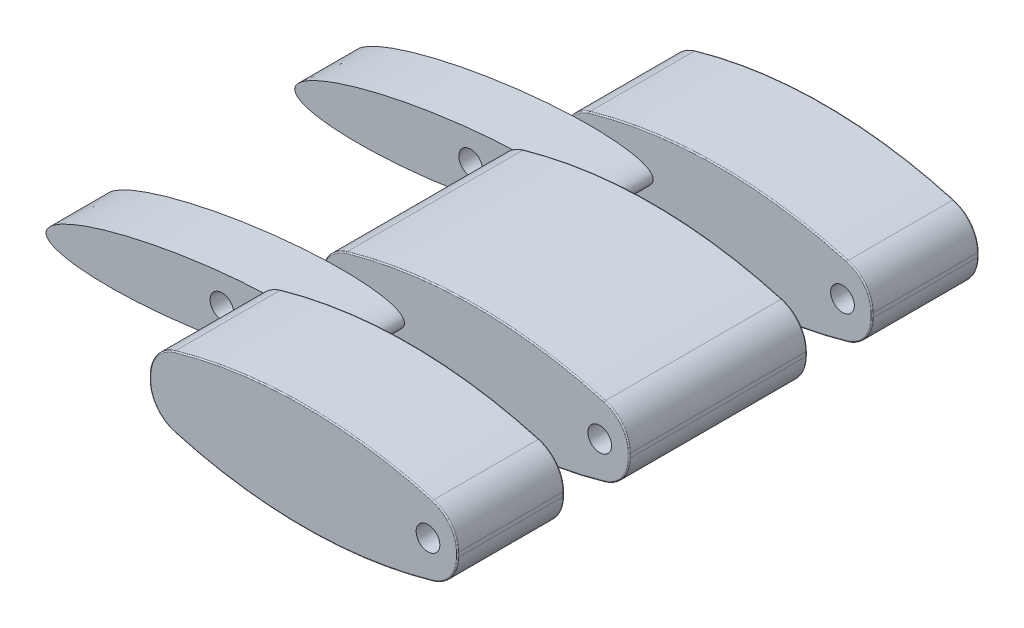
SolidWorks part; units mm, degrees
note: The reader was unsure of these and kept them because the rebuilt part matched: shared geometry of "Sketch6<2>".
ref_plane "Front Plane" through (0, 0, 0) normal (0, 0, 1) x (1, 0, 0)
ref_plane "Top Plane" through (0, 0, 0) normal (0, 1, 0) x (1, 0, 0)
ref_plane "Right Plane" through (0, 0, 0) normal (1, 0, 0) x (0, 0, -1)
sketch "Sketch1" plane through (0, 0, 0) normal (0, 0, 1) x (1, 0, 0)
  line L0 (0, -55) -> (0, 55) construction
  line L2 (-6.5, 0.0896) -> (-6.5, -0.0896)
  line L4 (6.5, 0.0896) -> (6.5, -0.0896)
  arc A0 (-5.45, 1.4833) -> (5.45, 1.4833) centre (0, -17.5045) cw
  arc A1 (-5.45, -1.4833) -> (5.45, -1.4833) centre (0, 17.5045) ccw
  arc A2 (5.45, 1.4833) -> (6.5, 0.0896) centre (5.05, 0.0896) cw
  arc A3 (5.45, -1.4833) -> (6.5, -0.0896) centre (5.05, -0.0896) ccw
  arc A4 (-5.45, -1.4833) -> (-6.5, -0.0896) centre (-5.05, -0.0896) cw
  arc A5 (-5.45, 1.4833) -> (-6.5, 0.0896) centre (-5.05, 0.0896) ccw
  dimension "D1" = 1.45
  dimension "D2" = 6.5
extrude "Boss-Extrude1" add sketch "Sketch1" along normal blind 22
sketch "Sketch2" plane through (0, 0, 0) normal (0, 1, 0) x (1, 0, 0)
  line L0 (-2.475, 0) -> (2.475, 0) construction
  line L1 (-10.8182, -4.5) -> (10.0029, -4.5)
  line L2 (-10.8182, -4.5) -> (-10.8182, -7.25)
  line L3 (-10.8182, -7.25) -> (10.0029, -7.25)
  line L4 (10.0029, -4.5) -> (10.0029, -7.25)
  line L5 (-9.7834, -14.75) -> (12.5428, -14.75)
  line L6 (-9.7834, -14.75) -> (-9.7834, -17.5)
  line L7 (-9.7834, -17.5) -> (12.5428, -17.5)
  line L8 (12.5428, -14.75) -> (12.5428, -17.5)
  line L9 (-5.45, -22) -> (5.45, -22) construction
  dimension "D1" = 4.5
  dimension "D2" = 4.5
  dimension "D3" = 2.75
  dimension "D4" = 2.75
extrude "Cut-Extrude1" cut sketch "Sketch2" against normal mid plane 22
sketch "Sketch3" plane through (0, 0, 22) normal (0, 0, 1) x (1, 0, 0)
  line L0 (12.1, 0) -> (-12.1, 0) construction
  line L1 (0, -2.475) -> (0, 2.475) construction
  circle A0 centre (5.25, 0) radius 0.5
  circle A1 centre (-5.25, 0) radius 0.5
  dimension "D1" = 1
  dimension "D2" = 1
  dimension "D3" = 5.25
  dimension "D4" = 5.25
extrude "Cut-Extrude2" cut sketch "Sketch3" against normal blind 21 from offset 0.5 offset against normal yes
fillet "Fillet1" radius 0.05 16 edges at (6.2081, 0.9621, 17.5) (6.5, 0, 17.5) (6.2081, -0.9621, 17.5) (0, -2.25, 17.5) (-6.2081, -0.9621, 17.5) (-6.5, 0, 17.5) (-6.2081, 0.9621, 17.5) (6.5, 0, 22) (6.2081, -0.9621, 22) (0, -2.25, 22) (-6.2081, -0.9621, 22) (-6.5, 0, 22) (-6.2081, 0.9621, 22) (0, 2.25, 22) (6.2081, 0.9621, 22) (0, 2.25, 17.5)
fillet "Fillet2" radius 0.05 16 edges at (6.2081, 0.9621, 7.25) (6.5, 0, 7.25) (6.2081, -0.9621, 7.25) (0, -2.25, 7.25) (-6.2081, -0.9621, 7.25) (-6.5, 0, 7.25) (-6.2081, 0.9621, 7.25) (-6.2081, 0.9621, 14.75) (-6.5, 0, 14.75) (-6.2081, -0.9621, 14.75) (0, -2.25, 14.75) (6.2081, -0.9621, 14.75) (6.5, 0, 14.75) (6.2081, 0.9621, 14.75) (0, 2.25, 7.25) (0, 2.25, 14.75)
fillet "Fillet3" radius 0.05 16 edges at (6.2081, 0.9621, 0) (6.5, 0, 0) (6.2081, -0.9621, 0) (0, -2.25, 0) (-6.2081, -0.9621, 0) (-6.5, 0, 0) (-6.2081, 0.9621, 0) (-6.5, 0, 4.5) (-6.2081, -0.9621, 4.5) (0, -2.25, 4.5) (6.2081, -0.9621, 4.5) (6.5, 0, 4.5) (6.2081, 0.9621, 4.5) (0, 2.25, 4.5) (0, 2.25, 0) (-6.2081, 0.9621, 4.5)
sketch "Sketch4" plane through (0, 0, 4.5) normal (0, 0, 1) x (1, 0, 0)
  circle A0 centre (5.25, 0) radius 0.5
  dimension "D1" = 1
extrude "Cut-Extrude3" cut sketch "Sketch4" against normal mid plane 60
sketch "Sketch6" plane through (0, 0, 22) normal (0, 0, 1) x (1, 0, 0)
  ellipse E0 centre (-9.0588, -0.5158) end of major axis (-2.7434, 0.3987) minor radius 1.231
extrude "Boss-Extrude2" add sketch "Sketch6" against normal blind 2.5 from offset 4.5 offset against normal yes
extrude "Boss-Extrude3" add sketch "Sketch6<2>" along normal blind 2.5 from offset 17.5 offset against normal yes
sketch "Sketch6<2>" plane through (0, 0, 22) normal (0, 0, 1) x (1, 0, 0) same geometry as "Sketch6"
sketch "Sketch7" plane through (0, 0, 17.5) normal (0, 0, 1) x (1, 0, 0)
  circle A0 centre (-7.9476, -0.3774) radius 0.5
  dimension "D1" = 1
extrude "Cut-Extrude6" cut sketch "Sketch7" against normal blind 22.5
sketch "Sketch8" plane through (0, 0, 0) normal (0, 1, 0) x (1, 0, 0)
  line L0 (-0.2, -20.7889) -> (0.2, -20.7889)
  line L1 (-0.2, -20.7889) -> (-0.2, -19.2889)
  line L2 (0.2, -20.7889) -> (0.2, -19.2889)
  line L3 (-0.2, -19.2889) -> (-0.45, -19.2889)
  line L4 (-0.45, -19.2889) -> (0, -18.6389)
  line L5 (0, -18.6389) -> (0.45, -19.2889)
  line L6 (0.45, -19.2889) -> (0.2, -19.2889)
  line L7 (0.2, -19.2889) -> (0.2001, -19.2946)
  dimension "D1" = 0.4
  dimension "D2" = 1.5
  dimension "D3" = 0.25
  dimension "D4" = 0.25
extrude "Cut-Extrude7" cut sketch "Sketch8" along normal offset from surface (7.95 mm away) 0.2 from offset 10 contours L2 L0 L1 L3 L4 L5 L6 offset against normal yes
fillet "Fillet4" radius 0.02 14 edges at (0, -2.25, 20.7889) (-0.2, -2.249, 20.0389) (-0.325, -2.2473, 19.2889) (-0.225, -2.2487, 18.964) (0.225, -2.2487, 18.964) (0.325, -2.2473, 19.2889) (0.2, -2.249, 20.0389) (0.225, -2.0487, 18.964) (-0.225, -2.0487, 18.964) (-0.325, -2.0473, 19.2889) (-0.2, -2.049, 20.0389) (0, -2.05, 20.7889) (0.2, -2.049, 20.0389) (0.325, -2.0473, 19.2889)
